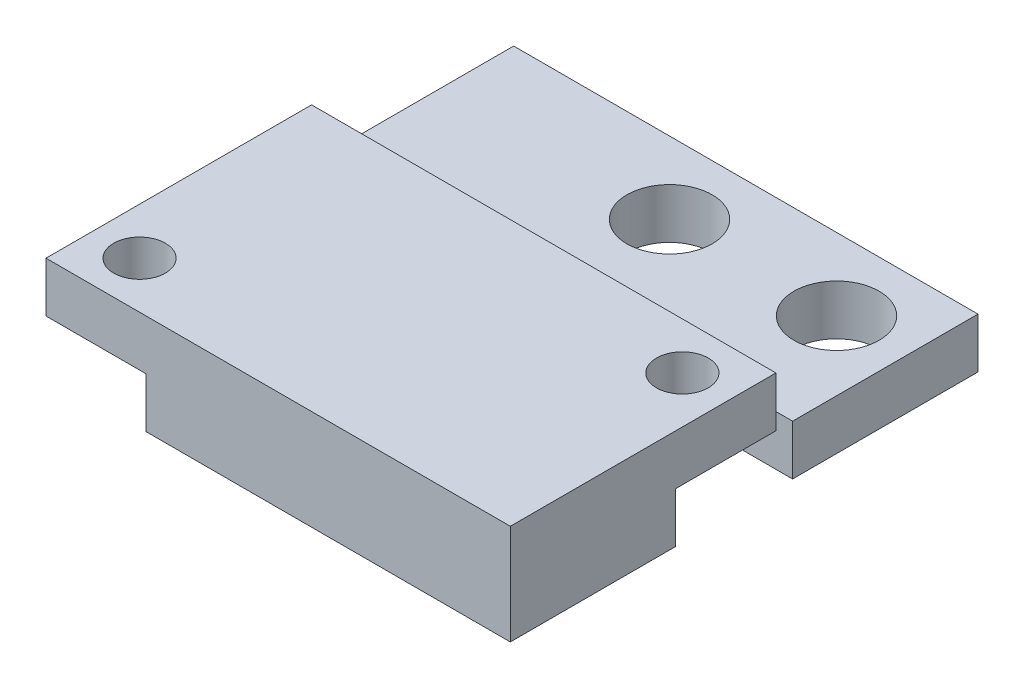
SolidWorks part; units mm, degrees
ref_plane "Front Plane" through (0, 0, 0) normal (0, 0, 1) x (1, 0, 0)
ref_plane "Top Plane" through (0, 0, 0) normal (0, 1, 0) x (1, 0, 0)
ref_plane "Right Plane" through (0, 0, 0) normal (1, 0, 0) x (0, 0, -1)
sketch "Sketch1" plane through (0, 0, 0) normal (0, 1, 0) x (1, 0, 0)
  line L0 (13.65, 23.68) -> (23.65, 23.68) construction
  line L1 (0, 0) -> (27.8, 0)
  line L2 (0, 0) -> (0, 28)
  line L3 (0, 28) -> (27.8, 28)
  line L4 (27.8, 0) -> (27.8, 28)
  circle A0 centre (13.65, 23.68) radius 2.55
  circle A1 centre (23.65, 23.68) radius 2.55
  dimension "D2" = 5.1
  dimension "D1" = 10
  dimension "D3" = 27.8
  dimension "D4" = 28
  dimension "D5" = 23.68
  dimension "D6" = 13.65
extrude "Boss-Extrude1" add sketch "Sketch1" along normal blind 3
sketch "Sketch2" plane through (0, 3, 0) normal (0, 1, 0) x (1, 0, 0)
  line L0 (27.8, 0) -> (27.8, 28) construction
  line L1 (0, 0) -> (27.8, 0)
  line L2 (0, 0) -> (0, 15.9)
  line L3 (0, 15.9) -> (27.8, 15.9)
  line L4 (27.8, 0) -> (27.8, 15.9)
  circle A0 centre (2.8, 2.8) radius 1.55
  circle A1 centre (25, 13.1) radius 1.55
  dimension "D2" = 3.1
  dimension "D1" = 15.9
  dimension "D3" = 2.8
  dimension "D4" = 2.8
  dimension "D5" = 2.8
  dimension "D6" = 2.8
extrude "Boss-Extrude2" add sketch "Sketch2" along normal blind 3
sketch "Sketch3" plane through (0, 0, 0) normal (0, -1, 0) x (1, 0, 0)
  line L0 (27.8, -28) -> (0, -28)
  line L1 (27.8, -28) -> (0, -28)
  line L2 (0, -28) -> (0, -15.9)
  line L3 (0, -28) -> (0, -15.9)
  line L4 (0, -15.9) -> (0, 0)
  line L6 (0, 0) -> (27.8, 0)
  line L8 (27.8, 0) -> (27.8, -15.9)
  line L10 (27.8, -15.9) -> (27.8, -28)
  line L11 (27.8, -15.9) -> (27.8, -28)
  line L12 (27.8, -28) -> (0, -28)
  line L13 (27.8, -28) -> (0, -28)
  line L14 (0, -28) -> (0, -15.9)
  line L15 (0, -28) -> (0, -15.9)
  line L16 (0, -15.9) -> (0, 0)
  line L17 (0, -15.9) -> (0, 0)
  line L18 (0, 0) -> (27.8, 0)
  line L20 (27.8, 0) -> (27.8, -15.9)
  line L21 (27.8, 0) -> (27.8, -15.9)
  line L22 (27.8, -15.9) -> (27.8, -28)
  line L23 (27.8, -15.9) -> (27.8, -28)
  line L25 (0, 0) -> (6, 0)
  line L26 (0, 0) -> (0, -6)
  line L27 (0, -6) -> (6, -6)
  line L28 (0, 0) -> (0, -15.9)
  line L29 (27.8, 0) -> (0, 0)
  line L30 (27.8, -15.9) -> (27.8, 0)
  line L31 (0, -15.9) -> (27.8, -15.9)
  line L32 (0, 0) -> (0, -15.9)
  line L34 (27.8, -15.9) -> (27.8, 0)
  line L36 (6, 0) -> (6, -6)
  line L37 (27.8, -15.9) -> (22.8, -15.9)
  line L38 (27.8, -15.9) -> (27.8, -10.9)
  line L39 (27.8, -10.9) -> (22.8, -10.9)
  line L40 (22.8, -15.9) -> (22.8, -10.9)
  line M16 (0, 0) -> (0, -28)
  line M19 (27.8, 0) -> (0, 0)
  dimension "D2" = 6
  dimension "D3" = 6
  dimension "D4" = 5
  dimension "D5" = 5
  dimension "D1" = 0
extrude "Cut-Extrude5" cut sketch "Sketch3" against normal blind 3 contours L36 L27 M19 M16 region at (3, 0, -3)
sketch "Sketch4" plane through (0, 0, 0) normal (0, -1, 0) x (1, 0, 0)
  line L5 (27.8, 0) -> (27.8, -28) construction
  line L6 (27.8, -16.9) -> (21.8, -16.9)
  line L7 (27.8, -16.9) -> (27.8, -9.9)
  line L8 (27.8, -9.9) -> (21.8, -9.9)
  line L9 (0, 0) -> (0, -15.9)
  line L10 (27.8, 0) -> (0, 0)
  line L11 (27.8, -15.9) -> (27.8, 0)
  line L12 (0, -15.9) -> (27.8, -15.9)
  line L13 (0, 0) -> (0, -15.9)
  line L14 (27.8, 0) -> (0, 0)
  line L15 (27.8, -15.9) -> (27.8, 0)
  line L16 (0, -15.9) -> (27.8, -15.9)
  line L17 (21.8, -16.9) -> (21.8, -9.9)
  line M16 (27.8, -28) -> (27.8, 0)
  dimension "D2" = 6
  dimension "D3" = 7
  dimension "D4" = 1
  dimension "D1" = 0
extrude "Cut-Extrude7" cut sketch "Sketch4" against normal blind 3 contours L17 L16 L7 L8 | L17 L6 L16 M16 region at (24.8, 0, -16.4) region at (24.8, 0, -12.9)
